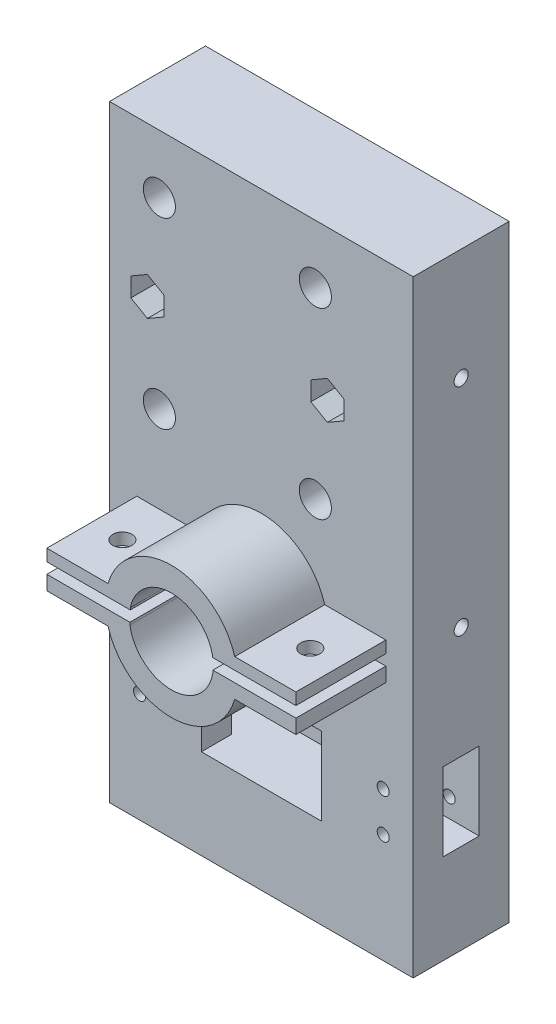
SolidWorks part; units mm, degrees
other "Markup1"
sketch "Sketch8" plane through (21.3115, 25, 0) normal (0.306, 0.1864, -0.9336) x (-0.9512, 0.0181, -0.3081)
ref_plane "Front Plane" through (0, 0, 0) normal (0, 0, 1) x (1, 0, 0)
ref_plane "Top Plane" through (0, 0, 0) normal (0, 1, 0) x (1, 0, 0)
ref_plane "Right Plane" through (0, 0, 0) normal (1, 0, 0) x (0, 0, -1)
sketch "Sketch1" plane through (0, 0, 0) normal (0, 0, 1) x (1, 0, 0)
  line L0 (0, 25) -> (0, -25) construction
  line L1 (21.3115, 25) -> (-21.3115, 25)
  line L2 (21.3115, 25) -> (21.3115, -25)
  line L3 (21.3115, -25) -> (-21.3115, -25)
  line L4 (-21.3115, 25) -> (-21.3115, -25)
  line L5 (21.3115, 25) -> (-21.3115, -25) construction
  line L6 (21.3115, -25) -> (-21.3115, 25) construction
  line L7 (-21.3115, 0) -> (21.3115, 0) construction
  circle A0 centre (-13, -15.25) radius 2.677
  circle A1 centre (13, -15.25) radius 2.677
  circle A2 centre (13, 15.25) radius 2.677
  circle A3 centre (-13, 15.25) radius 2.677
  point P0 (0, 0)
  dimension "D1" = 30.5
  dimension "D2" = 26
  dimension "D3" = 50
extrude "Boss-Extrude1" add sketch "Sketch1" along normal blind 16
sketch "Sketch2" plane through (0, 0, 0) normal (0, 0, 1) x (1, 0, 0)
  circle A0 centre (0, 0) radius 11.04
  dimension "D1" = 22.08
extrude "Cut-Extrude2" cut sketch "Sketch2" along normal blind 11
sketch "Sketch3" plane through (0, 0, 0) normal (0, 0, -1) x (-1, 0, 0)
  line L0 (0, 0) -> (-18.0234, 0) construction
  line L1 (0, 0) -> (0, 5.0894) construction
  circle A0 centre (-15, 0) radius 1.75
  circle A1 centre (15, 0) radius 1.75
  dimension "D1" = 15
  dimension "D2" = 3.5
extrude "Cut-Extrude3" cut sketch "Sketch3" against normal blind 10
sketch "Sketch9" plane through (0, 0, 0) normal (0, 0, -1) x (-1, 0, 0)
  line L0 (0, -11.04) -> (0, 11.04) construction
  line L1 (-15, 3.1754) -> (-17.75, 1.5877)
  line L2 (-17.75, 1.5877) -> (-17.75, -1.5877)
  line L3 (-17.75, -1.5877) -> (-15, -3.1754)
  line L4 (-15, -3.1754) -> (-12.25, -1.5877)
  line L5 (-12.25, -1.5877) -> (-12.25, 1.5877)
  line L6 (-12.25, 1.5877) -> (-15, 3.1754)
  line L7 (12.25, 1.5877) -> (15, 3.1754)
  line L8 (12.25, -1.5877) -> (12.25, 1.5877)
  line L9 (15, -3.1754) -> (12.25, -1.5877)
  line L10 (17.75, -1.5877) -> (15, -3.1754)
  line L11 (17.75, 1.5877) -> (17.75, -1.5877)
  line L12 (15, 3.1754) -> (17.75, 1.5877)
  circle A0 centre (-15, 0) radius 2.75 construction
  circle A1 centre (0, 0) radius 11.04 construction
  point P1 (-17.75, 0)
  dimension "D1" = 5.5
extrude "Cut-Extrude6" cut sketch "Sketch9" against normal through all from offset 5 offset against normal yes
sketch "Sketch30" plane through (0, -25, 0) normal (0, -1, 0) x (1, 0, 0)
  line L1 (-21.3115, 16) -> (21.3115, 16)
  line L2 (-21.3115, 16) -> (-21.3115, 0)
  line L3 (-21.3115, 0) -> (21.3115, 0)
  line L4 (21.3115, 16) -> (21.3115, 0)
extrude "Boss-Extrude8" add sketch "Sketch30" along normal blind 20.23
sketch "Sketch10" plane through (0, 0, 0) normal (0, 0, 1) x (1, 0, 0)
  line L0 (21.3115, -45.23) -> (-21.3115, -45.23)
  line L2 (-21.3115, -45.23) -> (-21.3115, -61.23)
  line L3 (-21.3115, -61.23) -> (21.3115, -61.23)
  line L4 (21.3115, -61.23) -> (21.3115, -45.23)
  dimension "D1" = 16
extrude "Boss-Extrude2" add sketch "Sketch10" along normal up to surface (16 mm away) up to face at (15, 0, 16)
sketch "Sketch14" plane through (-21.3115, 0, 0) normal (-1, 0, 0) x (0, 0, 1)
  line L0 (16, -61.23) -> (0, -61.23) construction
  line L1 (5, -61.23) -> (11, -61.23)
  line L2 (5, -61.23) -> (5, -48.23)
  line L3 (5, -48.23) -> (11, -48.23)
  line L4 (11, -61.23) -> (11, -48.23)
  line L7 (0, -61.23) -> (16, -61.23) construction
  point P6 (8, -61.23)
  point P7 (8, -61.23)
  dimension "D1" = 13
  dimension "D2" = 6
extrude "Cut-Extrude7" cut sketch "Sketch14" against normal through all
sketch "Sketch16" plane through (21.3115, 0, 0) normal (1, 0, 0) x (0, 0, -1)
  line L0 (-8, -48.23) -> (-8, 25)
  line L1 (-11, -48.23) -> (-5, -48.23) construction
  line L2 (-16, 25) -> (0, 25) construction
  line L4 (-16, 25) -> (0, 25)
  line L5 (-16, 25) -> (-16, -48.23)
  line L6 (-16, -48.23) -> (0, -48.23)
  line L7 (0, 25) -> (0, -48.23)
  line M6 (-11, -48.23) -> (-5, -48.23)
  line M9 (0, -61.23) -> (0, 25)
  line M10 (0, 25) -> (-16, 25)
  line M11 (-16, 25) -> (-16, -61.23)
extrude "Boss-Extrude3" add sketch "Sketch16" along normal blind 8 contours L6 L0 M11 M6 M10 | L6 L0 M6 M9 M10 region at (21.3115, -11.615, 12) region at (21.3115, -11.615, 4)
sketch "Sketch17" plane through (29.3115, 0, 0) normal (1, 0, 0) x (0, 0, -1)
  line L0 (-8, -48.23) -> (-8, 25)
  line L1 (-16, -48.23) -> (0, -48.23) construction
  line L2 (0, 25) -> (-16, 25) construction
  line L3 (-8, -11.615) -> (0, -11.615)
  line L4 (0, -48.23) -> (0, 25) construction
  circle A0 centre (-8, 6.385) radius 1.175
  circle A1 centre (-8, -29.615) radius 1.175
  point P8 (-8, -11.615)
  dimension "D2" = 2.35
  dimension "D1" = 18
extrude "Cut-Extrude9" cut sketch "Sketch17" against normal blind 8 contours L0 A0 | L0 A0 | A1 L0 | A1 L0 region at (29.3115, -29.615, 8.4987) region at (29.3115, 6.385, 8.4987) region at (29.3115, 6.385, 7.5013) region at (29.3115, -29.615, 7.5013)
sketch "Sketch18" plane through (0, 0, 0) normal (0, 0, -1) x (-1, 0, 0)
  line L0 (-25.3115, -48.23) -> (-25.3115, 25)
  line L1 (-29.3115, -48.23) -> (-21.3115, -48.23) construction
  line L2 (-29.3115, 25) -> (21.3115, 25) construction
  line L3 (-25.3115, -11.615) -> (-29.3115, -11.615)
  line L4 (-26.2115, 8.385) -> (-24.4115, 8.385)
  line L5 (-26.2115, 8.385) -> (-26.2115, 4.385)
  line L6 (-26.2115, 4.385) -> (-24.4115, 4.385)
  line L7 (-24.4115, 8.385) -> (-24.4115, 4.385)
  line L8 (-26.2115, 8.385) -> (-24.4115, 4.385) construction
  line L9 (-26.2115, 4.385) -> (-24.4115, 8.385) construction
  line L10 (-29.3115, -48.23) -> (-29.3115, 25) construction
  line L11 (-26.2115, -27.615) -> (-24.4115, -27.615)
  line L12 (-24.4115, -31.615) -> (-24.4115, -27.615)
  line L13 (-26.2115, -31.615) -> (-24.4115, -31.615)
  line L14 (-26.2115, -31.615) -> (-26.2115, -27.615)
  point P6 (-25.3115, 6.385)
  point P11 (-25.3115, -11.615)
  dimension "D1" = 18
  dimension "D2" = 4
  dimension "D3" = 1.8
extrude "Cut-Extrude10" cut sketch "Sketch18" against normal blind 10.2 contours L7 L4 L0 L6 | L5 L6 L0 L4 | L14 L11 L12 L13 region at (25.7615, 6.385, 0) region at (24.8615, 6.385, 0)
sketch "Sketch15" plane through (0, 0, 0) normal (0, 0, -1) x (-1, 0, 0)
  line L0 (21.3115, -61.23) -> (-21.3115, -61.23) construction
  line L1 (-29.3115, -23.2996) -> (21.3115, -23.2996)
  line L2 (-21.3115, -61.23) -> (-21.3115, -48.23)
  line L3 (-29.3115, -48.23) -> (-29.3115, 25) construction
  line L4 (-4, -23.2996) -> (-4, -61.23)
  line L7 (-21.3115, -61.23) -> (-21.3115, -48.23) construction
  line L8 (-21.3115, -48.23) -> (-21.3115, -61.23) construction
  line L9 (-21.3115, -54.73) -> (21.3115, -54.73)
  line L10 (21.3115, 25) -> (21.3115, -61.23) construction
  line L11 (21.3115, -54.73) -> (21.3115, -28)
  line L12 (21.3115, -28) -> (0, -28)
  line L13 (0, -28) -> (0, -61.23)
  circle A2 centre (16.3115, -58.03) radius 1
  circle A4 centre (16.3115, -51.43) radius 1
  point P11 (-21.3115, -61.23)
  dimension "D1" = 5
  dimension "D2" = 3.2
extrude "Cut-Extrude8" cut sketch "Sketch15" against normal through all and the other way through all contours A2 | A4
sketch "Sketch6" plane through (0, -48.23, 0) normal (0, -1, 0) x (1, 0, 0)
  line L0 (21.3115, 11) -> (-21.3115, 11) construction
  line L1 (4.517, 11) -> (-4.517, 11)
  line L2 (4.517, 11) -> (4.517, 14.85)
  line L3 (4.517, 14.85) -> (-4.517, 14.85)
  line L4 (-4.517, 11) -> (-4.517, 14.85)
  line L5 (4.517, 11) -> (-4.517, 14.85) construction
  line L6 (4.517, 14.85) -> (-4.517, 11) construction
  point P0 (0, 12.925)
  dimension "D1" = 3.85
extrude "Cut-Extrude5" cut sketch "Sketch6" against normal blind 50 and the other way through all
sketch "Sketch20" plane through (0, -48.23, 0) normal (0, -1, 0) x (-1, 0, 0)
  line L1 (-21.3115, -16) -> (-29.3115, -16)
  line L2 (-21.3115, -16) -> (-21.3115, 0)
  line L3 (-21.3115, 0) -> (-29.3115, 0)
  line L4 (-29.3115, -16) -> (-29.3115, 0)
extrude "Boss-Extrude5" add sketch "Sketch20" along normal up to surface (13 mm away) up to face at (0, -61.23, 13.2125)
sketch "Sketch21" plane through (0, -61.23, 0) normal (0, -1, 0) x (-1, 0, 0)
  line L0 (-29.3115, -16) -> (-29.3115, 0) construction
  line L1 (-21.3115, -11) -> (-29.3115, -11)
  line L2 (-21.3115, -11) -> (-21.3115, -5)
  line L3 (-21.3115, -5) -> (-29.3115, -5)
  line L4 (-29.3115, -11) -> (-29.3115, -5)
extrude "Cut-Extrude11" cut sketch "Sketch21" against normal up to surface (13 mm away) up to face at (0, -48.23, 9)
sketch "Sketch22" plane through (0, 0, 0) normal (0, 0, -1) x (-1, 0, 0)
  line L0 (21.3115, -61.23) -> (-29.3115, -61.23) construction
  line L1 (-29.3115, -61.23) -> (-29.3115, 25) construction
  circle A0 centre (-24.3115, -58.03) radius 1
  circle A3 centre (-24.3115, -51.43) radius 1
  dimension "D1" = 2
  dimension "D2" = 3.2
  dimension "D3" = 5
  dimension "D4" = 6.6
  dimension "D5" = 2
  dimension "D6" = 5
extrude "Cut-Extrude12" cut sketch "Sketch22" against normal through all
sketch "Sketch24" plane through (0, -61.23, 0) normal (0, -1, 0) x (1, 0, 0)
  line L1 (-21.3115, 5) -> (29.3115, 5)
  line L2 (-21.3115, 5) -> (-21.3115, 0)
  line L3 (-21.3115, 0) -> (29.3115, 0)
  line L4 (29.3115, 5) -> (29.3115, 0)
extrude "Boss-Extrude6" add sketch "Sketch24" along normal blind 15
sketch "Sketch25" plane through (0, 0, 5) normal (0, 0, 1) x (1, 0, 0)
  line L0 (29.3115, -76.23) -> (-21.3115, -76.23) construction
  line L1 (-21.3115, -76.23) -> (29.3115, -76.23)
  line L2 (-21.3115, -76.23) -> (-21.3115, -61.23)
  line L3 (-21.3115, -61.23) -> (29.3115, -61.23)
  line L4 (29.3115, -76.23) -> (29.3115, -61.23)
extrude "Boss-Extrude7" add sketch "Sketch25" along normal up to surface (11 mm away) up to face at (23.3115, -58.03, 16)
sketch "Sketch26" plane through (0, -76.23, 0) normal (0, -1, 0) x (1, 0, 0)
  line L0 (4, 16) -> (4, 0)
  line L1 (29.3115, 16) -> (-21.3115, 16) construction
  line L2 (-21.3115, 0) -> (29.3115, 0) construction
  line L3 (4, 8) -> (-21.3115, 8)
  line L4 (-21.3115, 16) -> (-21.3115, 0) construction
  circle A0 centre (-14, 8) radius 1
  circle A1 centre (22, 8) radius 1
  dimension "D1" = 2
  dimension "D2" = 18
extrude "Cut-Extrude13" cut sketch "Sketch26" against normal blind 10 contours L3 A0 | L3 A0 | A1 region at (-14, -76.23, 7.5756) region at (-14, -76.23, 8.4244) region at (22, -76.23, 8)
sketch "Sketch27" plane through (0, 0, 0) normal (0, 0, -1) x (-1, 0, 0)
  line L0 (-24.4115, -31.615) -> (-24.4115, -27.615) construction
  line L1 (-24.0015, -71.33) -> (-20.0015, -71.33)
  line L2 (-24.0015, -71.33) -> (-24.0015, -73.13)
  line L3 (-24.0015, -73.13) -> (-20.0015, -73.13)
  line L4 (-20.0015, -71.33) -> (-20.0015, -73.13)
  line L5 (-24.0015, -71.33) -> (-20.0015, -73.13) construction
  line L6 (-24.0015, -73.13) -> (-20.0015, -71.33) construction
  line L8 (-26.2115, -31.615) -> (-24.4115, -31.615) construction
  line L12 (-29.3115, -76.23) -> (-29.3115, 25) construction
  line L13 (21.3115, -76.23) -> (-29.3115, -76.23) construction
  line L14 (-29.3115, -49.5626) -> (21.3115, -49.5626)
  line L15 (21.3115, 25) -> (21.3115, -76.23) construction
  line L16 (-4, -49.5626) -> (-4, -76.23)
  line L17 (16.0015, -73.13) -> (12.0015, -73.13)
  line L18 (12.0015, -71.33) -> (12.0015, -73.13)
  line L19 (16.0015, -71.33) -> (12.0015, -71.33)
  line L20 (16.0015, -71.33) -> (16.0015, -73.13)
  point P0 (-22.0015, -72.23)
  dimension "D1" = 7.31
  dimension "D2" = 3.1
extrude "Cut-Extrude14" cut sketch "Sketch27" against normal blind 10.2 contours L4 L1 L2 L3 | L20 L19 L18 L17 region at (22.0015, -72.23, 0) region at (-14.0015, -72.23, 0)
sketch "Sketch29" plane through (0, 0, 16) normal (0, 0, 1) x (1, 0, 0)
  line L0 (-16.3115, -51.43) -> (24.3115, -58.03)
  line L1 (24.3115, -51.43) -> (-16.3115, -58.03)
  line L2 (-16.3115, -51.43) -> (24.3115, -51.43)
  line L3 (-16.3115, -51.43) -> (-16.3115, -58.03)
  line L4 (-16.3115, -58.03) -> (24.3115, -58.03)
  line L5 (24.3115, -51.43) -> (24.3115, -58.03)
  line L7 (-6, -48.23) -> (14, -48.23)
  line L8 (-6, -48.23) -> (-6, -61.23)
  line L9 (-6, -61.23) -> (14, -61.23)
  line L10 (14, -48.23) -> (14, -61.23)
  line L11 (-6, -48.23) -> (14, -61.23) construction
  line L12 (-6, -61.23) -> (14, -48.23) construction
  circle A0 centre (-16.3115, -51.43) radius 1 construction
  point P4 (4, -54.73)
  dimension "D1" = 13
  dimension "D2" = 20
extrude "Cut-Extrude15" cut sketch "Sketch29" against normal up to surface (5 mm away) contours L10 L7 L8 L2 | L10 L2 L8 L0 L1 | L0 L8 L1 | L10 L4 L8 L9 | L10 L0 L1 L8 L4 | L10 L1 L0 region at (4, -52.718, 16) region at (-2.6667, -54.73, 16) region at (4, -49.83, 16) region at (10.6667, -54.73, 16) region at (4, -56.742, 16) region at (4, -59.63, 16) up to face at (-16.3115, -59.03, 11)
sketch "Sketch31" plane through (0, 0, 0) normal (0, 0, -1) x (-1, 0, 0)
  line L5 (-4.5, 14.04) -> (4.5, 14.04)
  line L6 (-4.5, 14.04) -> (-4.5, 8.04)
  line L7 (-4.5, -8.04) -> (4.5, -8.04)
  line L8 (-4.5, -8.04) -> (-4.5, -14.04)
  line L9 (-4.5, -14.04) -> (4.5, -14.04)
  line L10 (4.5, -8.04) -> (4.5, -14.04)
  line L11 (-4.5, -8.04) -> (4.5, -14.04) construction
  line L12 (-4.5, -14.04) -> (4.5, -8.04) construction
  line L13 (-4.5, 8.04) -> (4.5, 8.04)
  line L14 (4.5, 14.04) -> (4.5, 8.04)
  line L15 (-4.5, 14.04) -> (4.5, 8.04) construction
  line L16 (-4.5, 8.04) -> (4.5, 14.04) construction
  circle A1 centre (0, 0) radius 11.04 construction
  point P0 (-11.04, 0)
  point P1 (0, 11.04)
  point P8 (0, -11.04)
  dimension "D1" = 6
  dimension "D2" = 9
  dimension "D3" = 9
  dimension "D4" = 6
extrude "Cut-Extrude16" cut sketch "Sketch31" against normal up to surface (11 mm away) up to face at (0, 1.1266, 11)
sketch "Sketch32" plane through (0, 0, 16) normal (0, 0, 1) x (1, 0, 0)
  line L2 (-21.3115, 25) -> (-21.3115, -76.23) construction
  line L24 (14.5594, -29.7152) -> (24.7586, -29.7152)
  line L25 (-14.3528, -31.6808) -> (-2.8528, -31.6808)
  line L27 (-14.3528, -33.4838) -> (-2.9147, -33.4838)
  line L29 (-2.8528, -31.3568) -> (-2.8528, -31.6808)
  line L30 (-2.9147, -33.8911) -> (-2.9147, -33.4838)
  line L31 (10.9117, -33.8911) -> (10.9117, -33.4838)
  line L32 (10.8592, -31.6808) -> (10.8498, -31.3568)
  line L33 (10.8592, -31.6808) -> (22.3498, -31.6808)
  line L34 (10.9117, -33.4838) -> (22.3498, -33.4838)
  line L35 (-16.7615, -29.7152) -> (-6.5624, -29.7152)
  line L36 (-16.7615, -29.7152) -> (-16.7615, -31.6808)
  line L37 (-16.7615, -35.8689) -> (-6.5624, -35.8689)
  line L38 (24.7586, -29.7152) -> (24.7586, -31.6808)
  line L39 (14.5594, -35.8689) -> (24.7586, -35.8689)
  line L40 (-14.3528, -31.6808) -> (-16.7615, -31.6808)
  line L41 (-14.3528, -33.4838) -> (-16.7615, -33.4838)
  line L42 (22.3498, -31.6808) -> (24.7586, -31.6808)
  line L43 (22.3498, -33.4838) -> (24.7586, -33.4838)
  line L44 (-16.7615, -33.4838) -> (-16.7615, -35.8689)
  line L45 (24.7586, -33.4838) -> (24.7586, -35.8689)
  arc A0 (-2.9147, -33.8911) -> (10.9117, -33.8911) centre (3.9985, -32.792) ccw
  arc A1 (-6.5624, -35.8689) -> (14.5594, -35.8689) centre (3.9985, -32.792) ccw
  arc A2 (14.5594, -29.7152) -> (-6.5624, -29.7152) centre (3.9985, -32.792) ccw
  arc A3 (10.8498, -31.3568) -> (-2.8528, -31.3568) centre (3.9985, -32.792) ccw
  dimension "D1" = 25.31
extrude "Boss-Extrude9" add sketch "Sketch32" along normal blind 15
sketch "Sketch35" plane through (0, 0, 16) normal (0, 0, 1) x (1, 0, 0)
  circle A0 centre (3.9985, -32.792) radius 7
extrude "Cut-Extrude17" cut sketch "Sketch35" against normal through all
sketch "Sketch46" plane through (0, -76.23, 0) normal (0, -1, 0) x (1, 0, 0)
  line L0 (29.3115, 16) -> (-21.3115, 16) construction
  line L2 (-16.7615, 31) -> (-16.7615, 16) construction
  line L3 (24.7586, 31) -> (24.7586, 16) construction
  circle A0 centre (-11.6615, 23.5) radius 1.6
  circle A1 centre (19.6586, 23.5) radius 1.6
  dimension "D1" = 7.5
  dimension "D3" = 5.1
  dimension "D2" = 5.1
extrude "Cut-Extrude29" cut sketch "Sketch46" against normal through all
